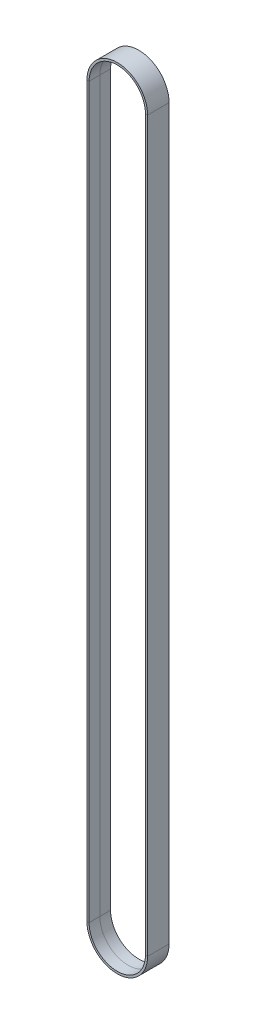
SolidWorks part; units mm, degrees
ref_plane "Спереди" through (0, 0, 0) normal (0, 0, 1) x (1, 0, 0)
ref_plane "Сверху" through (0, 0, 0) normal (0, 1, 0) x (1, 0, 0)
ref_plane "Справа" through (0, 0, 0) normal (1, 0, 0) x (0, 0, -1)
sketch "Эскиз2" plane through (0, 0, 0) normal (0, 0, 1) x (1, 0, 0)
  line L0 (0, 0) -> (1, 0) construction
  line L1 (0, 0) -> (0, 1) construction
  line L2 (26.25, 0) -> (26.25, -678.6787)
  line L3 (-26.25, -678.6787) -> (-26.25, 0)
  arc A0 (-26.25, 0) -> (26.25, 0) centre (0, 0) cw
  arc A1 (26.25, -678.6787) -> (-26.25, -678.6787) centre (0, -678.6787) cw
ref_plane "Плоскость1" through (0, 0, 0) normal (0, 0, 1) x (1, 0, 0)
sketch "Эскиз3" plane through (0, 0, 0) normal (0, 0, 1) x (1, 0, 0)
  line L0 (-26.25, -678.6787) -> (-26.25, 0) construction
  line L1 (26.25, 0) -> (26.25, -678.6787) construction
  line L2 (-26.25, -678.6787) -> (-26.25, 0)
  line L3 (26.25, 0) -> (26.25, -678.6787)
  arc A0 (26.25, 0) -> (-26.25, 0) centre (0, 0) ccw construction
  arc A1 (-26.25, -678.6787) -> (26.25, -678.6787) centre (0, -678.6787) ccw construction
  arc A2 (26.25, 0) -> (-26.25, 0) centre (0, 0) ccw
  arc A3 (-26.25, -678.6787) -> (26.25, -678.6787) centre (0, -678.6787) ccw
ref_plane "Плоскость2" through (0, 0, 0) normal (0, 1, 0) x (1, 0, 0)
sketch "Эскиз4" plane through (0, 0, 0) normal (0, 1, 0) x (1, 0, 0)
  line L0 (-11.2834, 10) -> (-8.8306, 10) construction
  line L2 (26.25, 0) -> (26.25, -10)
  line L3 (26.25, -10) -> (28.25, -10)
  line L6 (26.25, 0) -> (26.25, 10)
  line L7 (26.25, 10) -> (28.25, 10)
  line L9 (-8.8306, -10) -> (-11.2834, -10) construction
  line L10 (28.25, -10) -> (28.25, 10)
  dimension "D1" = 2
  dimension "D2" = 2
sweep "По траектории1" add profiles "Эскиз4" path "Эскиз3"
